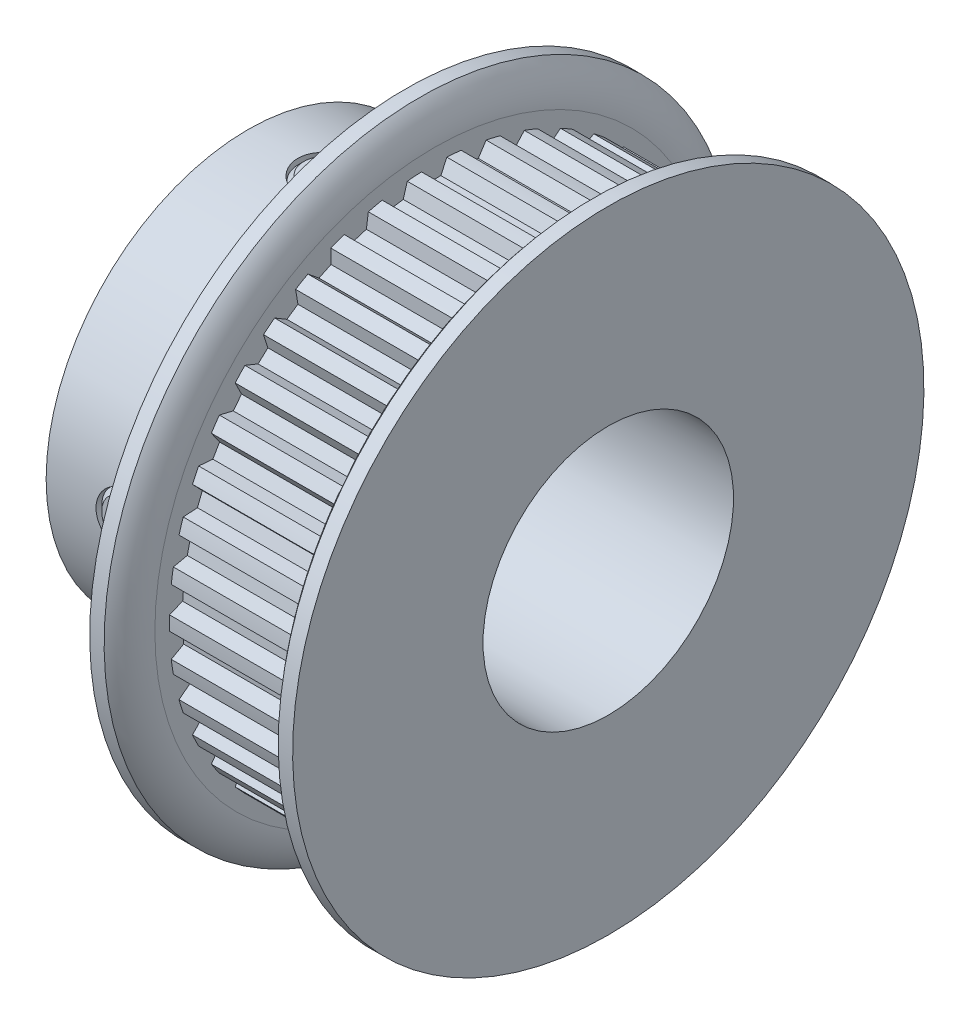
SolidWorks part; units mm, degrees
ref_plane "Front Plane" through (0, 0, 0) normal (0, 0, 1) x (1, 0, 0)
ref_plane "Top Plane" through (0, 0, 0) normal (0, 1, 0) x (1, 0, 0)
ref_plane "Right Plane" through (0, 0, 0) normal (1, 0, 0) x (0, 0, -1)
sketch "Sketch2" plane through (0, 0, 0) normal (1, 0, 0) x (0, 0, -1)
  line L3 (0, 0) -> (0, 12.7635) construction
  line L6 (0, -13.2715) -> (0, -13.589) construction
  line L7 (-0.5715, 13.2592) -> (-0.3383, 12.759)
  line L8 (0.5715, 13.2592) -> (0.3383, 12.759)
  line L9 (-0.5715, 13.2592) -> (-0.6441, 13.4148)
  line L10 (0.5715, 13.2592) -> (0.6441, 13.4148)
  line L12 (-0.3383, 12.759) -> (0.3383, 12.759)
  line L14 (0, 13.2715) -> (0, 13.589) construction
  line L15 (0, 0) -> (0, -1.143) construction
  circle A0 centre (0, 0) radius 13.589 construction
  circle A1 centre (0, 0) radius 12.7635 construction
  circle A2 centre (0, 0) radius 13.2715 construction
  arc A7 (0.6441, 13.4148) -> (-0.6441, 13.4148) centre (0, 0) ccw
  point P5 (0, 13.4303)
  dimension "D3" = 0.3175
  dimension "D1" = 50
sketch "Sketch1" plane through (0, 0, 0) normal (0, 0, 1) x (1, 0, 0)
  line L0 (-9.1313, 0) -> (9.1313, 0) construction
  line L1 (-9.1313, 3.175) -> (9.1313, 3.175)
  line L2 (-9.1313, 3.175) -> (-9.1313, 10.2362)
  line L3 (-1.1557, 16.002) -> (-0.4254, 16.002)
  line L4 (0.3048, 13.589) -> (0.3048, 14.1605)
  line L5 (0.3048, 14.732) -> (0.3048, 13.589) construction
  line L6 (0.3048, 13.589) -> (7.6708, 13.589)
  line L7 (7.6708, 13.589) -> (7.6708, 14.1605)
  line L8 (7.6708, 13.589) -> (9.1313, 13.589) construction
  line L9 (8.4011, 16.002) -> (9.1313, 16.002)
  line L10 (9.1313, 16.002) -> (9.1313, 3.175)
  line L11 (8.4011, 13.589) -> (8.4011, 16.002) construction
  line L12 (-5.1435, 10.2362) -> (-5.1435, 3.175) construction
  line L13 (-1.1557, 16.002) -> (-1.1557, 10.2362)
  line L14 (-1.1557, 10.2362) -> (-9.1313, 10.2362)
  arc A0 (7.6708, 14.1605) -> (8.4011, 16.002) centre (10.3578, 14.1605) cw
  arc A1 (0.3048, 14.1605) -> (-0.4254, 16.002) centre (-2.3822, 14.1605) ccw
  dimension "Bore Size" = 6.35
  dimension "Overall Width" = 18.2626
  dimension "Inside Width" = 7.366
  dimension "OD" = 32.004
  dimension "D2" = 27.178
  dimension "D3" = 1.143
  dimension "D4" = 0.5715
  dimension "Outside Width" = 10.287
revolve "Revolve1" add sketch "Sketch1" angle 360 mid plane about L0
sketch "Sketch4" plane through (0.3048, 0, 0) normal (1, 0, 0) x (0, 0, -1)
  circle A0 centre (0, 0) radius 13.4303
  circle A2 centre (0, 0) radius 13.589
  circle A3 centre (0, 0) radius 13.589 construction
extrude "Cut-Extrude2" cut sketch "Sketch4" along normal up to surface (7.366 mm away) up to face at (7.6708, -13.589, 0)
sketch "Sketch3" plane through (0.3048, 0, 0) normal (1, 0, 0) x (0, 0, -1)
  line L2 (-0.5715, 13.2592) -> (-0.3383, 12.759) construction
  line L3 (-0.3383, 12.759) -> (0.3383, 12.759) construction
  line L4 (0.5715, 13.2592) -> (0.3383, 12.759) construction
  line L5 (-0.6441, 13.4148) -> (-0.3383, 12.759)
  line L6 (-0.3383, 12.759) -> (0.3383, 12.759)
  line L7 (0.6441, 13.4148) -> (0.3383, 12.759)
  arc A1 (0.6441, 13.4148) -> (-0.6441, 13.4148) centre (0, 0) ccw construction
  arc A2 (0.6441, 13.4148) -> (-0.6441, 13.4148) centre (0, 0) ccw
extrude "Cut-Extrude1" cut sketch "Sketch3" along normal up to surface (7.366 mm away) up to face at (7.6708, -14.1605, 0)
pattern_circular "CirPattern1" count 42 over 360 of "Cut-Extrude1"
sketch "Sketch5" plane through (0, 0, 0) normal (0, 0, 1) x (1, 0, 0)
  line L1 (7.6708, 14.1605) -> (7.6708, -14.1605) construction
  point P0 (7.6708, 0)
sketch "Sketch6" plane through (0, 0, 0) normal (0, 1, 0) x (1, 0, 0)
  line L0 (-9.1313, 0) -> (-6.604, 0) construction
  line L1 (-9.1313, 16.002) -> (-9.1313, -16.002) construction
  line L2 (-1.1557, 0) -> (-3.683, 0) construction
  line L4 (-1.1557, 16.002) -> (-1.1557, -16.002) construction
  circle A0 centre (-5.1435, 0) radius 1.4605
  dimension "D1" = 2.921
extrude "Cut-Extrude3" cut sketch "Sketch6" along normal through all
sketch "Sketch7" plane through (0, 0, 0) normal (0, 0, 1) x (1, 0, 0)
  line L0 (-6.3119, 10.2362) -> (-5.1435, 10.2362)
  line L1 (-6.5659, 9.9822) -> (-6.5659, 3.81)
  line L2 (-6.5659, 3.81) -> (-6.3119, 3.556)
  line L3 (-6.3119, 3.556) -> (-5.1435, 3.556)
  line L4 (-5.1435, 3.556) -> (-5.1435, 10.2362) construction
  line L5 (-1.1557, 10.2362) -> (-9.1313, 10.2362) construction
  line L6 (-6.5659, 9.9822) -> (-6.3119, 10.2362)
  line L8 (-5.1435, 10.2362) -> (-5.1435, 3.556)
  point P0 (-6.5659, 10.2362)
  point P4 (-6.5659, 3.556)
  dimension "D1" = 2.8448
  dimension "D2" = 0.381
revolve "Revolve2" add sketch "Sketch7" angle 360 mid plane about L4
sketch "Sketch8" plane through (0, 10.2362, 0) normal (0, 1, 0) x (1, 0, 0)
  line L1 (-5.1435, 0.8212) -> (-5.8547, 0.4106)
  line L2 (-5.8547, 0.4106) -> (-5.8547, -0.4106)
  line L3 (-5.8547, -0.4106) -> (-5.1435, -0.8212)
  line L4 (-5.1435, -0.8212) -> (-4.4323, -0.4106)
  line L5 (-4.4323, -0.4106) -> (-4.4323, 0.4106)
  line L6 (-4.4323, 0.4106) -> (-5.1435, 0.8212)
  circle A0 centre (-5.1435, 0) radius 0.7112 construction
  dimension "D1" = 1.4224
extrude "Cut-Extrude4" cut sketch "Sketch8" against normal blind 1.016
pattern_circular "CirPattern2" count 2 over 90 about axis through (-9.1313, 0, 0) along (-1, 0, 0) of "Cut-Extrude3" reverse direction yes
pattern_circular "CirPattern3" count 2 over 90 reverse direction yes of bodies 107
sketch "Sketch9" plane through (-9.1313, 0, 0) normal (-1, 0, 0) x (0, 0, 1)
  circle A0 centre (0, 0) radius 6.35
extrude "Cut-Extrude5" cut sketch "Sketch9" against normal through all
equation "\"D3@Sketch2\" = (\"hs@Sketch2\"-\"ht@Sketch2\")/2"
equation "\"D2@Sketch1\" = \"PD@Sketch2\""
equation "\"D3@Sketch1\" = \"hs@Sketch2\""
equation "\"D4@Sketch1\" = \"D3@Sketch1\"/2"
